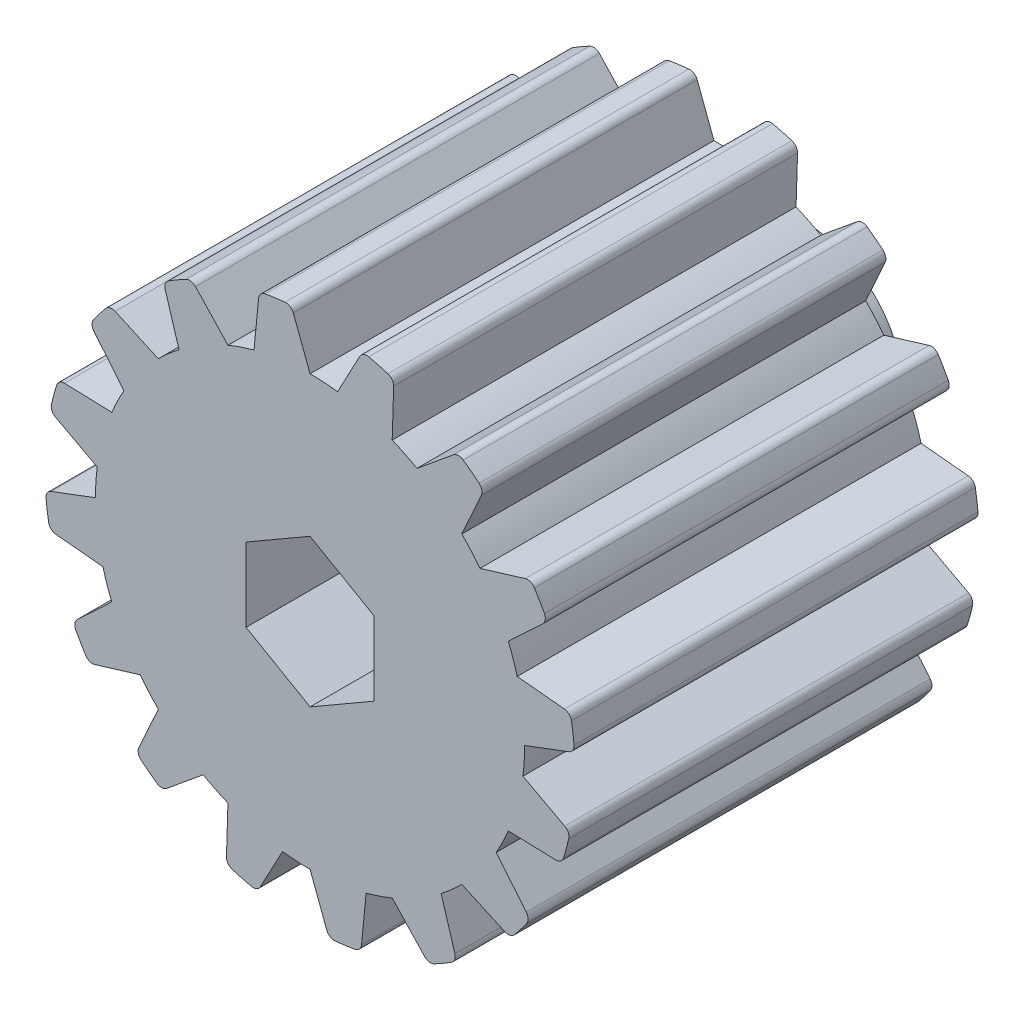
SolidWorks part; units mm, degrees
ref_plane "Alzado" through (0, 0, 0) normal (0, 0, 1) x (1, 0, 0)
ref_plane "Planta" through (0, 0, 0) normal (0, 1, 0) x (1, 0, 0)
ref_plane "Vista lateral" through (0, 0, 0) normal (1, 0, 0) x (0, 0, -1)
sketch "Croquis2" plane through (0, 0, 0) normal (0, 0, 1) x (1, 0, 0)
  line L0 (0, 0) -> (0, 7.9702) construction
  line L2 (-2.0817, 7.6936) -> (-1.9112, 9.4453)
  line L3 (-1.0408, 7.8319) -> (0, 0) construction
  line L4 (0, 7.9702) -> (-0.6221, 9.6166)
  line L5 (1.021, 7.9046) -> (1.8489, 9.4577)
  line L6 (3.0501, 7.3635) -> (3.1053, 9.1227)
  line L7 (3.9682, 6.9122) -> (5.3274, 8.0302)
  line L8 (5.6358, 5.6358) -> (6.3601, 7.2399)
  line L9 (6.3113, 4.8674) -> (7.9949, 5.3803)
  line L10 (7.3635, 3.0501) -> (8.6465, 4.2549)
  line L11 (7.6936, 2.0817) -> (9.4453, 1.9112)
  line L12 (7.9702, 0) -> (9.6166, 0.6221)
  line L13 (7.9046, -1.021) -> (9.4577, -1.8489)
  line L14 (7.3635, -3.0501) -> (9.1227, -3.1053)
  line L15 (6.9122, -3.9682) -> (8.0302, -5.3274)
  line L16 (5.6358, -5.6358) -> (7.2399, -6.3601)
  line L17 (4.8674, -6.3113) -> (5.3803, -7.9949)
  line L18 (3.0501, -7.3635) -> (4.2549, -8.6465)
  line L19 (2.0817, -7.6936) -> (1.9112, -9.4453)
  line L20 (0, -7.9702) -> (0.6221, -9.6166)
  line L21 (-1.021, -7.9046) -> (-1.8489, -9.4577)
  line L22 (-3.0501, -7.3635) -> (-3.1053, -9.1227)
  line L23 (-3.9682, -6.9122) -> (-5.3274, -8.0302)
  line L24 (-5.6358, -5.6358) -> (-6.3601, -7.2399)
  line L25 (-6.3113, -4.8674) -> (-7.9949, -5.3803)
  line L26 (-7.3635, -3.0501) -> (-8.6465, -4.2549)
  line L27 (-7.6936, -2.0817) -> (-9.4453, -1.9112)
  line L28 (-7.9702, 0) -> (-9.6166, -0.6221)
  line L29 (-7.9046, 1.021) -> (-9.4577, 1.8489)
  line L30 (-7.3635, 3.0501) -> (-9.1227, 3.1053)
  line L31 (-6.9122, 3.9682) -> (-8.0302, 5.3274)
  line L32 (-5.6358, 5.6358) -> (-7.2399, 6.3601)
  line L33 (-4.8674, 6.3113) -> (-5.3803, 7.9949)
  line L34 (-3.0501, 7.3635) -> (-4.2549, 8.6465)
  arc A0 (-4.8674, 6.3113) -> (-5.6358, 5.6358) centre (0, 0) ccw
  arc A1 (-7.5914, 6.2764) -> (-8.0413, 5.6886) centre (0, 0) ccw
  arc A2 (-1.6636, 9.7085) -> (-1.9112, 9.4453) centre (-1.6129, 9.4128) ccw
  arc A3 (-0.9298, 9.806) -> (-0.6221, 9.6166) centre (-0.9015, 9.5074) cw
  arc A4 (2.1783, 9.6061) -> (1.8489, 9.4577) centre (2.112, 9.3135) ccw
  arc A5 (2.8935, 9.4154) -> (3.1053, 9.1227) centre (2.8054, 9.1286) cw
  arc A6 (5.6886, 8.0413) -> (5.3274, 8.0302) centre (5.5153, 7.7964) ccw
  arc A7 (6.2764, 7.5914) -> (6.3601, 7.2399) centre (6.0852, 7.3602) cw
  arc A8 (8.3328, 5.2523) -> (7.9949, 5.3803) centre (8.0791, 5.0923) ccw
  arc A9 (8.7037, 4.6117) -> (8.6465, 4.2549) centre (8.4387, 4.4712) cw
  arc A10 (9.7085, 1.6636) -> (9.4453, 1.9112) centre (9.4128, 1.6129) ccw
  arc A11 (9.806, 0.9298) -> (9.6166, 0.6221) centre (9.5074, 0.9015) cw
  arc A12 (9.6061, -2.1783) -> (9.4577, -1.8489) centre (9.3135, -2.112) ccw
  arc A13 (9.4154, -2.8935) -> (9.1227, -3.1053) centre (9.1286, -2.8054) cw
  arc A14 (8.0413, -5.6886) -> (8.0302, -5.3274) centre (7.7964, -5.5153) ccw
  arc A15 (7.5914, -6.2764) -> (7.2399, -6.3601) centre (7.3602, -6.0852) cw
  arc A16 (5.2523, -8.3328) -> (5.3803, -7.9949) centre (5.0923, -8.0791) ccw
  arc A17 (4.6117, -8.7037) -> (4.2549, -8.6465) centre (4.4712, -8.4387) cw
  arc A18 (1.6636, -9.7085) -> (1.9112, -9.4453) centre (1.6129, -9.4128) ccw
  arc A19 (0.9298, -9.806) -> (0.6221, -9.6166) centre (0.9015, -9.5074) cw
  arc A20 (-2.1783, -9.6061) -> (-1.8489, -9.4577) centre (-2.112, -9.3135) ccw
  arc A21 (-2.8935, -9.4154) -> (-3.1053, -9.1227) centre (-2.8054, -9.1286) cw
  arc A22 (-5.6886, -8.0413) -> (-5.3274, -8.0302) centre (-5.5153, -7.7964) ccw
  arc A23 (-6.2764, -7.5914) -> (-6.3601, -7.2399) centre (-6.0852, -7.3602) cw
  arc A24 (-8.3328, -5.2523) -> (-7.9949, -5.3803) centre (-8.0791, -5.0923) ccw
  arc A25 (-8.7037, -4.6117) -> (-8.6465, -4.2549) centre (-8.4387, -4.4712) cw
  arc A26 (-9.7085, -1.6636) -> (-9.4453, -1.9112) centre (-9.4128, -1.6129) ccw
  arc A27 (-9.806, -0.9298) -> (-9.6166, -0.6221) centre (-9.5074, -0.9015) cw
  arc A28 (-9.6061, 2.1783) -> (-9.4577, 1.8489) centre (-9.3135, 2.112) ccw
  arc A29 (-9.4154, 2.8935) -> (-9.1227, 3.1053) centre (-9.1286, 2.8054) cw
  arc A30 (-8.0413, 5.6886) -> (-8.0302, 5.3274) centre (-7.7964, 5.5153) ccw
  arc A31 (-7.5914, 6.2764) -> (-7.2399, 6.3601) centre (-7.3602, 6.0852) cw
  arc A32 (-5.2523, 8.3328) -> (-5.3803, 7.9949) centre (-5.0923, 8.0791) ccw
  arc A33 (-4.6117, 8.7037) -> (-4.2549, 8.6465) centre (-4.4712, 8.4387) cw
  arc A34 (-4.6117, 8.7037) -> (-5.2523, 8.3328) centre (0, 0) ccw
  arc A35 (-0.9298, 9.806) -> (-1.6636, 9.7085) centre (0, 0) ccw
  arc A36 (2.8935, 9.4154) -> (2.1783, 9.6061) centre (0, 0) ccw
  arc A37 (6.2764, 7.5914) -> (5.6886, 8.0413) centre (0, 0) ccw
  arc A38 (8.7037, 4.6117) -> (8.3328, 5.2523) centre (0, 0) ccw
  arc A39 (9.4154, -2.8935) -> (9.6061, -2.1783) centre (0, 0) ccw
  arc A40 (7.5914, -6.2764) -> (8.0413, -5.6886) centre (0, 0) ccw
  arc A41 (-9.4154, 2.8935) -> (-9.6061, 2.1783) centre (0, 0) ccw
  arc A42 (-9.806, -0.9298) -> (-9.7085, -1.6636) centre (0, 0) ccw
  arc A43 (-8.7037, -4.6117) -> (-8.3328, -5.2523) centre (0, 0) ccw
  arc A44 (-6.2764, -7.5914) -> (-5.6886, -8.0413) centre (0, 0) ccw
  arc A45 (-2.8935, -9.4154) -> (-2.1783, -9.6061) centre (0, 0) ccw
  arc A46 (0.9298, -9.806) -> (1.6636, -9.7085) centre (0, 0) ccw
  arc A47 (4.6117, -8.7037) -> (5.2523, -8.3328) centre (0, 0) ccw
  arc A48 (-2.0817, 7.6936) -> (-3.0501, 7.3635) centre (0, 0) ccw
  arc A49 (1.021, 7.9046) -> (0, 7.9702) centre (0, 0) ccw
  arc A50 (3.9682, 6.9122) -> (3.0501, 7.3635) centre (0, 0) ccw
  arc A51 (6.3113, 4.8674) -> (5.6358, 5.6358) centre (0, 0) ccw
  arc A52 (7.6936, 2.0817) -> (7.3635, 3.0501) centre (0, 0) ccw
  arc A53 (7.9046, -1.021) -> (7.9702, 0) centre (0, 0) ccw
  arc A54 (9.806, 0.9298) -> (9.7085, 1.6636) centre (0, 0) ccw
  arc A55 (6.9122, -3.9682) -> (7.3635, -3.0501) centre (0, 0) ccw
  arc A56 (4.8674, -6.3113) -> (5.6358, -5.6358) centre (0, 0) ccw
  arc A57 (2.0817, -7.6936) -> (3.0501, -7.3635) centre (0, 0) ccw
  arc A58 (-1.021, -7.9046) -> (0, -7.9702) centre (0, 0) ccw
  arc A59 (-3.9682, -6.9122) -> (-3.0501, -7.3635) centre (0, 0) ccw
  arc A60 (-6.3113, -4.8674) -> (-5.6358, -5.6358) centre (0, 0) ccw
  arc A61 (-7.6936, -2.0817) -> (-7.3635, -3.0501) centre (0, 0) ccw
  arc A62 (-7.9046, 1.021) -> (-7.9702, 0) centre (0, 0) ccw
  arc A63 (-6.9122, 3.9682) -> (-7.3635, 3.0501) centre (0, 0) ccw
  dimension "D1" = 2.1
  dimension "D2" = 19.7
  dimension "D3" = 15.9404
  dimension "D6" = 0.6
  dimension "D4" = 1.76
extrude "Saliente-Extruir1" add sketch "Croquis2" along normal blind 15
sketch "Croquis5" plane through (0, 0, 0) normal (0, 0, -1) x (-1, 0, 0)
  circle A0 centre (0, 0) radius 4.5
  dimension "D1" = 9
extrude "Saliente-Extruir2" add sketch "Croquis5" along normal blind 6
scale "Escala1" scale about origin uniform scaling yes scale factor 1.5
sketch "Croquis7" plane through (0, 0, -9) normal (0, 0, -1) x (-1, 0, 0)
  circle A0 centre (0, 0) radius 10
  dimension "D1" = 20
extrude "Cortar-Extruir3" cut sketch "Croquis7" against normal blind 5.8 and the other way through all
sketch "Croquis8" plane through (0, 0, -3.2) normal (0, 0, -1) x (-1, 0, 0)
  circle A3 centre (0, 0) radius 5.5
  dimension "D1" = 11
extrude "Saliente-Extruir3" add sketch "Croquis8" along normal blind 1.87
sketch "Croquis10" plane through (0, 0, 22.5) normal (0, 0, 1) x (1, 0, 0)
  line L0 (0, 4) -> (0, -5.201) construction
  line L1 (0, 4) -> (-3.4641, 2) construction
  line L2 (-3.4641, 2) -> (-3.4641, -2) construction
  line L3 (-3.4641, -2) -> (0, -4) construction
  line L4 (0, -4) -> (3.4641, -2) construction
  line L5 (3.4641, -2) -> (3.4641, 2) construction
  line L6 (3.4641, 2) -> (0, 4) construction
  line L8 (0, 4.1155) -> (-3.5641, 2.0577)
  line L9 (-3.5641, 2.0577) -> (-3.5641, -2.0577)
  line L10 (-3.5641, -2.0577) -> (0, -4.1155)
  line L11 (0, -4.1155) -> (3.5641, -2.0577)
  line L12 (3.5641, -2.0577) -> (3.5641, 2.0577)
  line L13 (3.5641, 2.0577) -> (0, 4.1155)
  circle A0 centre (0, 0) radius 4 construction
  circle A1 centre (0, 0) radius 4 construction
  circle A3 centre (0, 0) radius 3.5641 construction
  dimension "D1" = 8
  dimension "D2" = 0.1
extrude "Cortar-Extruir4" cut sketch "Croquis10" against normal through all both and the other way through all
